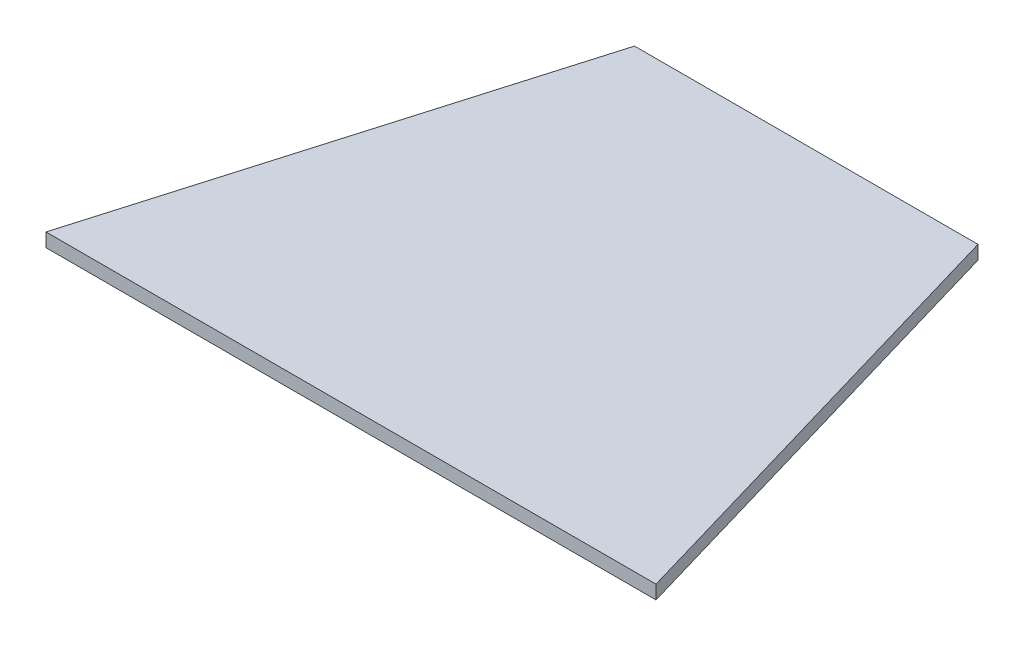
SolidWorks part; units mm, degrees
ref_plane "Front Plane" through (0, 0, 0) normal (0, 0, 1) x (1, 0, 0)
ref_plane "Top Plane" through (0, 0, 0) normal (0, 1, 0) x (1, 0, 0)
ref_plane "Right Plane" through (0, 0, 0) normal (1, 0, 0) x (0, 0, -1)
sketch "Sketch1" plane through (0, 0, 0) normal (0, 1, 0) x (1, 0, 0)
  line L0 (0, 0) -> (134, 0)
  line L1 (0, 0) -> (29.2799, 100)
  line L2 (134, 0) -> (104.7201, 100)
  line L3 (67, 0) -> (67, 100) construction
  line L4 (29.2799, 100) -> (104.7201, 100)
extrude "Boss-Extrude1" add sketch "Sketch1" along normal blind 3
